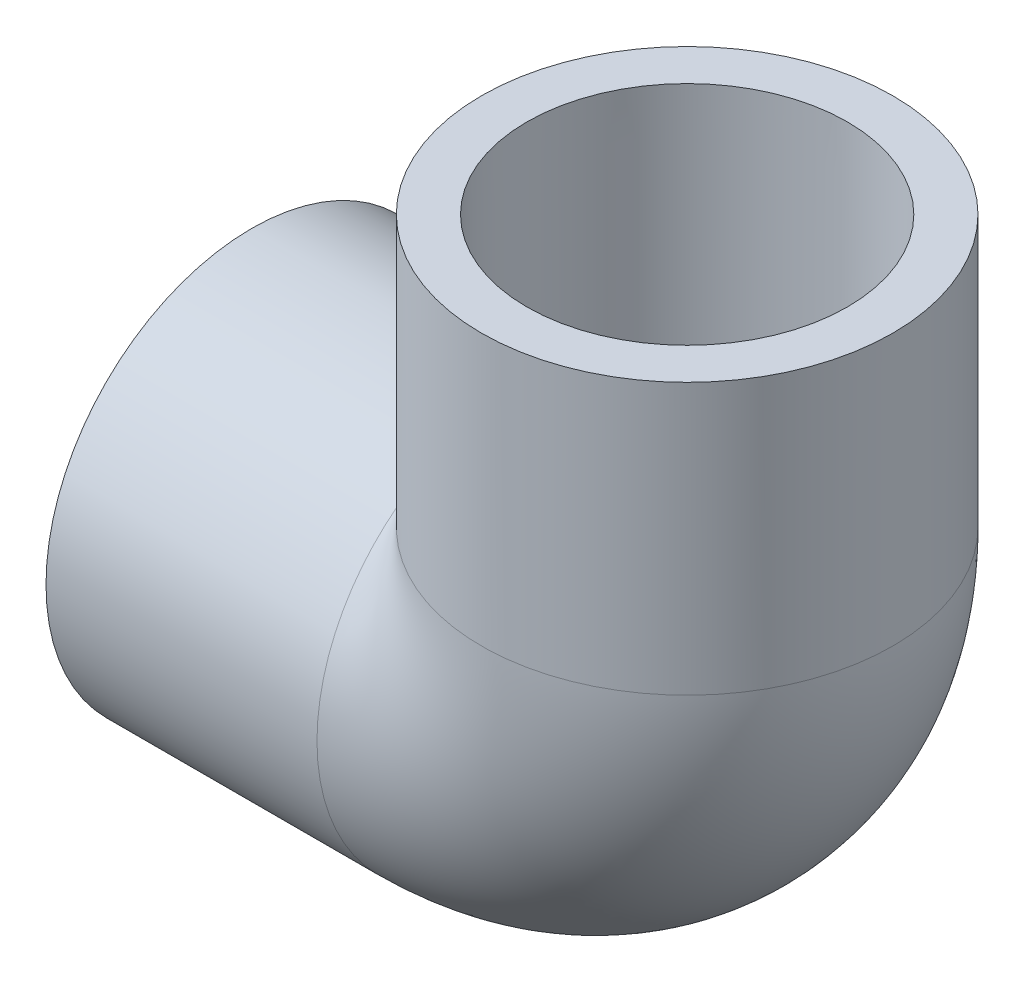
SolidWorks part; units mm, degrees
note: '?' marks a value the reader was unsure of.
ref_plane "Front Plane" through (0, 0, 0) normal (0, 0, 1) x (1, 0, 0)
ref_plane "Top Plane" through (0, 0, 0) normal (0, 1, 0) x (1, 0, 0)
ref_plane "Right Plane" through (0, 0, 0) normal (1, 0, 0) x (0, 0, -1)
sketch "Sketch0" plane through (0, 0, 0) normal (0, 0, 1) x (1, 0, 0)
  line L0 (-45.72, 0) -> (0, 0) construction
  line L1 (0, 0) -> (0, 45.72) construction
  line L2 (-17.272, 0) -> (0, 0) construction
  line L3 (0, 0) -> (0, 17.272) construction
  line L4 (-45.72, 21.59) -> (-45.72, -21.59) construction
  line L5 (-17.272, 16.637) -> (-45.72, 16.8275) construction
  line L6 (-17.272, 16.637) -> (-17.272, -16.637) construction
  line L7 (-17.272, -16.637) -> (-45.72, -16.8275) construction
  line L8 (-45.72, 16.8275) -> (-45.72, -16.8275) construction
  line L9 (-21.59, 45.72) -> (21.59, 45.72) construction
  line L10 (-16.8275, 45.72) -> (16.8275, 45.72) construction
  line L11 (16.8275, 45.72) -> (16.637, 17.272) construction
  line L12 (16.637, 17.272) -> (-16.637, 17.272) construction
  line L13 (-16.637, 17.272) -> (-16.8275, 45.72) construction
  line L14 (-17.272, 12.1539) -> (-17.272, -12.1539) construction
  line L18 (-12.1539, 17.272) -> (12.1539, 17.272) construction
  dimension "H" = 45.72
  dimension "G" = 17.272
  dimension "M" = 43.18
  dimension "OD A" = 33.655
  dimension "OD B" = 33.274
  dimension "ID" = 24.3078
sketch "Sketch1" plane through (0, 0, 0) normal (0, 0, 1) x (1, 0, 0)
  line L0 (-45.72, 0) -> (0, 0) construction
  line L1 (-45.72, 0) -> (0, 0) construction
  line L3 (-45.72, -21.59) -> (-17.272, -21.59)
  line L4 (-45.72, -21.59) -> (-45.72, -16.8275)
  line L5 (-45.72, -16.8275) -> (-17.272, -16.637)
  line L6 (-17.272, -21.59) -> (-17.272, -16.637)
revolve "Revolve1" add sketch "Sketch1" angle 360 about L1
sketch "Sketch2" plane through (0, 0, 0) normal (0, 0, 1) x (1, 0, 0)
  line L0 (16.8275, 45.72) -> (16.637, 17.272)
  line L1 (16.637, 17.272) -> (21.59, 17.272)
  line L2 (21.59, 17.272) -> (21.59, 45.72)
  line L3 (21.59, 45.72) -> (16.8275, 45.72)
  line L4 (0, 0) -> (0, 45.72) construction
  line L5 (0, 0) -> (0, 45.72) construction
revolve "Revolve2" add sketch "Sketch2" angle 360 about L5
sketch "Sketch3" plane through (-17.272, 0, 0) normal (1, 0, 0) x (0, 0, -1)
  circle A0 centre (0, 0) radius 12.1539
  circle A1 centre (0, 0) radius 21.59
sketch "Sketch4" plane through (0, 0, 0) normal (0, 0, 1) x (1, 0, 0)
  line L0 (-45.72, 0) -> (0, 0) construction
  line L1 (0, 0) -> (0, 45.72) construction
  line L2 (-45.72, 0) -> (-17.272, 0) construction
  line L3 (0, 17.272) -> (0, 45.72) construction
  arc A0 (-17.272, 0) -> (0, 17.272) centre (-17.272, 17.272) ccw
sweep "Sweep1" add profiles "Sketch3" path "Sketch4"
other "CPoint1" parameters "Diameter"=25.4, "StubLength"=19.05
ref_axis "Axis1" through (-27.272, 0, 0) along (1, 0, 0)?
other "CPoint2" parameters "Diameter"=25.4, "StubLength"=19.05
ref_axis "Axis2" through (0, 27.272, 0) along (0, -1, 0)?
other "RPoint1"
